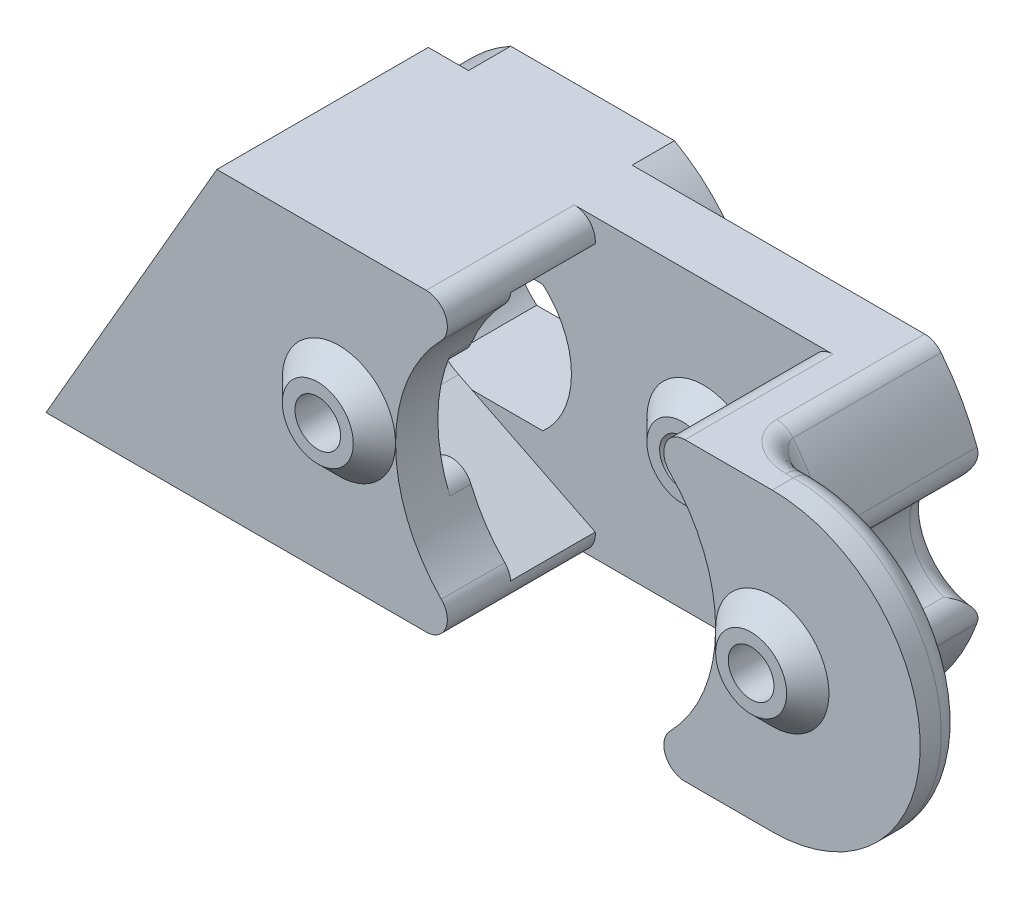
SolidWorks part; units mm, degrees
ref_plane "Front Plane" through (0, 0, 0) normal (0, 0, 1) x (1, 0, 0)
ref_plane "Top Plane" through (0, 0, 0) normal (0, 1, 0) x (1, 0, 0)
ref_plane "Right Plane" through (0, 0, 0) normal (1, 0, 0) x (0, 0, -1)
sketch "Sketch1" plane through (0, 0, 0) normal (0, 0, 1) x (1, 0, 0)
  line L0 (-20.5, 0) -> (20.5, 0) construction
  line L1 (-20.5, -14) -> (-48.2128, -14)
  line L2 (20.5, -14) -> (-20.5, -14)
  line L3 (20.5, -14) -> (20.5, 14) construction
  line L4 (20.5, 14) -> (-20.5, 14)
  line L5 (-20.5, -14) -> (-20.5, 14) construction
  line L6 (20.5, -14) -> (-20.5, 14) construction
  line L7 (20.5, 14) -> (-20.5, -14) construction
  line L8 (-48.2128, -14) -> (-32.047, 14)
  line L9 (-32.047, 14) -> (-20.5, 14)
  circle A0 centre (-20.5, 0) radius 2.159
  circle A1 centre (20.5, 0) radius 2.159
  circle A2 centre (0, 0) radius 2.159
  circle A3 centre (-20.5, 0) radius 16 construction
  circle A4 centre (20.5, 0) radius 16 construction
  arc A5 (20.5, 14) -> (20.5, -14) centre (20.5, 0) cw
  point P14 (20.5, 0)
  dimension "D1" = 41
  dimension "D2" = 4.318
  dimension "D3" = 32
  dimension "D4" = 60
  dimension "D5" = 17
  dimension "D6" = 2
extrude "Boss-Extrude1" add sketch "Sketch1" against normal blind 20
sketch "Sketch2" plane through (0, 0, 0) normal (0, 0, 1) x (1, 0, 0)
  circle A0 centre (-20.5, 0) radius 2.159
  circle A1 centre (-20.5, 0) radius 5.359
  circle A2 centre (20.5, 0) radius 2.159
  circle A3 centre (20.5, 0) radius 5.359
  circle A4 centre (20.5, 0) radius 2.159 construction
  dimension "D1" = 3.2
extrude "Boss-Extrude2" add sketch "Sketch2" along normal blind 2
chamfer "Chamfer1" distance 2 angle 45 2 edges at (25.859, 0, 2) (-15.141, 0, 2)
sketch "Sketch3" plane through (0, 0, 0) normal (0, 0, 1) x (1, 0, 0)
  circle A0 centre (0, 0) radius 15.141
extrude "Cut-Extrude1" cut sketch "Sketch3" against normal blind 14
fillet "Fillet1" radius 2 4 edges at (5.7663, -14, -7) (5.7663, 14, -7) (-5.7663, 14, -7) (-5.7663, -14, -7)
sketch "Sketch4" plane through (0, 0, -14) normal (0, 0, 1) x (1, 0, 0)
  line L0 (-25.7915, 6) -> (-15.2085, 6)
  line L1 (-25.7915, -6) -> (-15.2085, -6)
  arc A0 (-15.2085, -6) -> (-15.2085, 6) centre (-20.5, 0) ccw
  arc A1 (-25.7915, 6) -> (-25.7915, -6) centre (-20.5, 0) ccw
  dimension "D1" = 16
  dimension "D2" = 12
extrude "Cut-Extrude2" cut sketch "Sketch4" against normal through all
sketch "Sketch5" plane through (0, 0, -14) normal (0, 0, 1) x (1, 0, 0)
  line L0 (-23.1754, 5.3705) -> (-6.7514, 13.5524)
  line L1 (-23.1754, -5.3705) -> (-6.7514, -13.5524)
  arc A0 (-6.7514, -13.5524) -> (-6.7514, 13.5524) centre (0, 0) ccw
  arc A1 (-23.1754, 5.3705) -> (-23.1754, -5.3705) centre (-20.5, 0) ccw
  arc A2 (-15.2085, -6) -> (-15.2085, 6) centre (-20.5, 0) ccw construction
  arc A3 (-10.8117, 10.5998) -> (-15.141, 0) centre (0, 0) ccw construction
  dimension "D1" = 12
extrude "Cut-Extrude3" cut sketch "Sketch5" along normal blind 8
sketch "Sketch6" plane through (0, 0, -14) normal (0, 0, 1) x (1, 0, 0)
  circle A0 centre (0, 0) radius 5.359
  circle A1 centre (0, 0) radius 2.159
  circle A2 centre (0, 0) radius 2.159 construction
  dimension "D1" = 3.2
extrude "Boss-Extrude3" add sketch "Sketch6" along normal blind 2
chamfer "Chamfer2" distance 2 angle 45 1 edges at (5.359, 0, -12)
sketch "Sketch7" plane through (0, 0, -20) normal (0, 0, -1) x (-1, 0, 0)
  line L0 (-25.1646, 33.0949) -> (-9.926, 18.6659)
  line L1 (-8.8618, -19.194) -> (-25.4323, -32.8896)
  arc A0 (-9.926, 18.6659) -> (-20.5413, 4.9998) centre (0, 0) ccw
  arc A1 (-10.8117, 10.5998) -> (-10.8117, -10.5998) centre (0, 0) ccw construction
  arc A2 (-25.1646, 33.0949) -> (-25.4323, -32.8896) centre (0, 0) ccw
  arc A3 (-20.5413, -4.9998) -> (-20.5413, 4.9998) centre (-20.5, 0) ccw
  arc A4 (-20.5413, -4.9998) -> (-8.8618, -19.194) centre (0, 0) ccw
  dimension "D1" = 6
  dimension "D2" = 10
extrude "Cut-Extrude4" cut sketch "Sketch7" against normal blind 16
fillet "Fillet2" radius 2 11 edges at (15.8411, -14, -12) (18.1706, -14, -4) (34.5, 0, -4) (18.1706, 14, -4) (18.7395, 9.7863, -4) (15.5, 0, -4) (15.5, 0, -20) (15.8411, 14, -12) (18.7395, -9.7863, -4) (20.5413, -4.9998, -12) (20.5413, 4.9998, -12)
sketch "Sketch8" plane through (0, 0, -20) normal (0, 0, -1) x (-1, 0, 0)
  line L0 (15.2085, 6) -> (25.7915, 6) construction
  line L1 (15.2085, 6) -> (25.7915, 6)
  line L2 (25.7915, -6) -> (15.2085, -6) construction
  line L3 (25.7915, -6) -> (15.2085, -6)
  arc A0 (25.7915, -6) -> (25.7915, 6) centre (20.5, 0) ccw construction
  arc A1 (15.2085, 6) -> (15.2085, -6) centre (20.5, 0) ccw construction
  arc A2 (25.7915, -6) -> (25.7915, 6) centre (20.5, 0) ccw
  arc A3 (15.2085, 6) -> (15.2085, -6) centre (20.5, 0) ccw
extrude "Extrude-Thin1" add sketch "Sketch8" along normal blind 4 thin thin type one direction wall 8
sketch "Sketch9" plane through (0, 0, -6) normal (0, 0, -1) x (-1, 0, 0)
  circle A0 centre (20.5, 0) radius 6
extrude "Cut-Extrude5" cut sketch "Sketch9" against normal blind 2
fillet "Fillet3" radius 2 2 edges at (-14.9634, -2.3122, -5) (-14.9634, 2.3122, -5)
